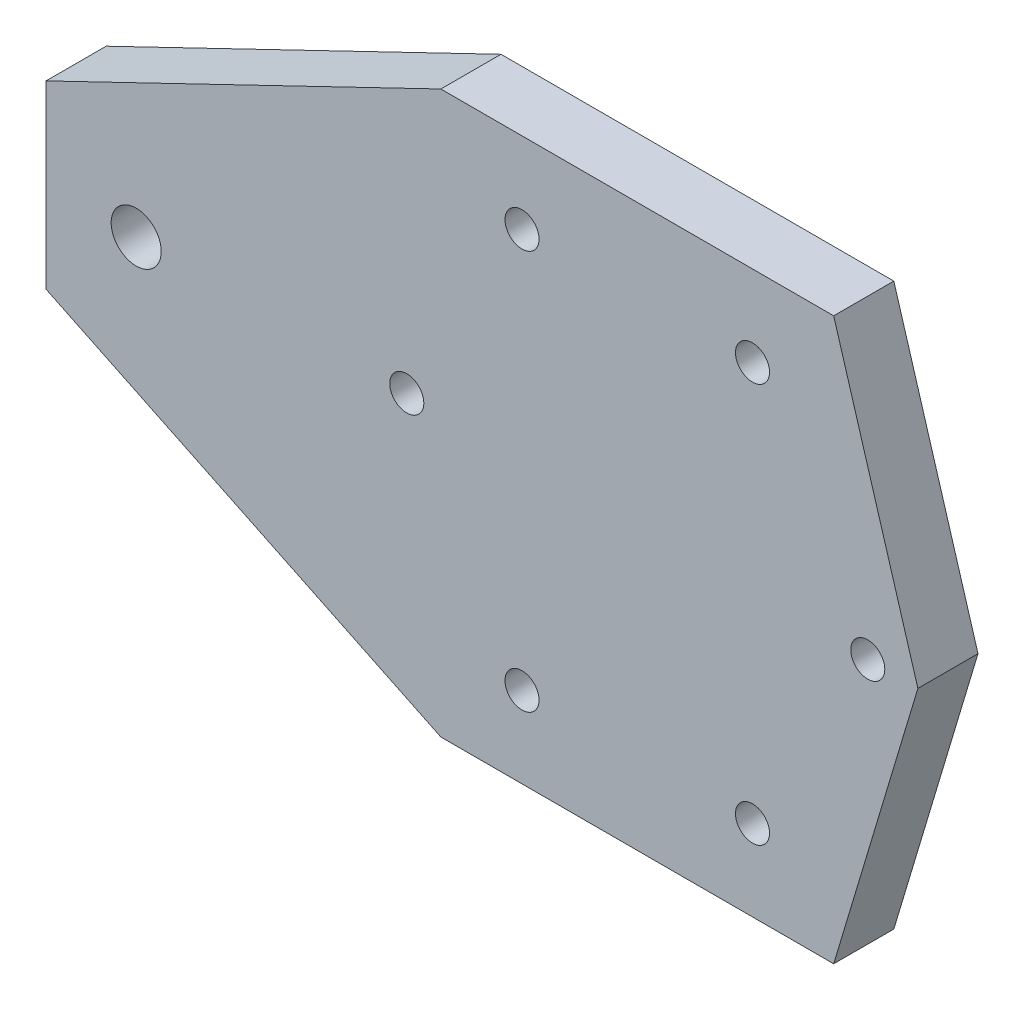
SolidWorks part; units mm, degrees
ref_plane "Front Plane" through (0, 0, 0) normal (0, 0, 1) x (1, 0, 0)
ref_plane "Top Plane" through (0, 0, 0) normal (0, 1, 0) x (1, 0, 0)
ref_plane "Right Plane" through (0, 0, 0) normal (1, 0, 0) x (0, 0, -1)
sketch "SK_Crank_Plate" plane through (0, 0, 0) normal (0, 0, 1) x (1, 0, 0)
  line L0 (-59, -9) -> (-19.6, -28)
  line L1 (-19.6, -28) -> (19.6, -28)
  line L2 (19.6, -28) -> (28, 0)
  line L3 (28, 0) -> (19.6, 28)
  line L4 (19.6, 28) -> (-19.6, 28)
  line L5 (-19.6, 28) -> (-59, 9)
  line L6 (-59, 9) -> (-59, -9)
  circle A0 centre (23, 0) radius 1.7
  circle A1 centre (11.5, 19.9186) radius 1.7
  circle A2 centre (-11.5, 19.9186) radius 1.7
  circle A3 centre (-23, 0) radius 1.7
  circle A4 centre (-11.5, -19.9186) radius 1.7
  circle A5 centre (11.5, -19.9186) radius 1.7
  circle A6 centre (-50, 0) radius 2.5
  dimension "D14_SK_Crank_Plate" = 3.4
  dimension "D16_SK_Crank_Plate" = 3.4
  dimension "D19_SK_Crank_Plate" = 3.4
  dimension "D22_SK_Crank_Plate" = 3.4
  dimension "D24_SK_Crank_Plate" = 3.4
  dimension "D27_SK_Crank_Plate" = 3.4
  dimension "D30_SK_Crank_Plate" = 5
  dimension "P1" = 59
  dimension "P2" = 9
  dimension "P3" = 19.6
  dimension "P4" = 28
  dimension "P5" = 19.6
  dimension "P6" = 28
  dimension "P7" = 28
  dimension "P8" = 19.6
  dimension "P9" = 28
  dimension "P10" = 19.6
  dimension "P11" = 28
  dimension "P12" = 59
  dimension "P13" = 9
  dimension "P15" = 23
  dimension "P17" = 11.5
  dimension "P18" = 19.9186
  dimension "P20" = 11.5
  dimension "P21" = 19.9186
  dimension "P23" = 23
  dimension "P25" = 11.5
  dimension "P26" = 19.9186
  dimension "P28" = 11.5
  dimension "P29" = 19.9186
  dimension "P31" = 50
extrude "Crank_Plate" add sketch "SK_Crank_Plate" along normal blind 6
sketch "SK_Pilot_Recess" plane through (0, 0, 0) normal (0, 0, 1) x (1, 0, 0)
  circle A0 centre (0, 0) radius 17.15
  dimension "D1_SK_Pilot_Recess" = 34.3
extrude "Pilot_Recess" cut sketch "SK_Pilot_Recess" along normal blind 2.2
ref_plane "PL_BallMid" through (0, 0, 3) normal (0, 0, 1) x (1, 0, 0)
sketch "SK_Ball" plane through (0, 0, 3) normal (0, 0, 1) x (1, 0, 0)
  point P0 (-50, 0)
  dimension "P1" = 50
ref_axis "AX_Joint" through (0, 0, -0.3) along (0, 0, 1)
equation "\"Crank_radius\" = 50"
